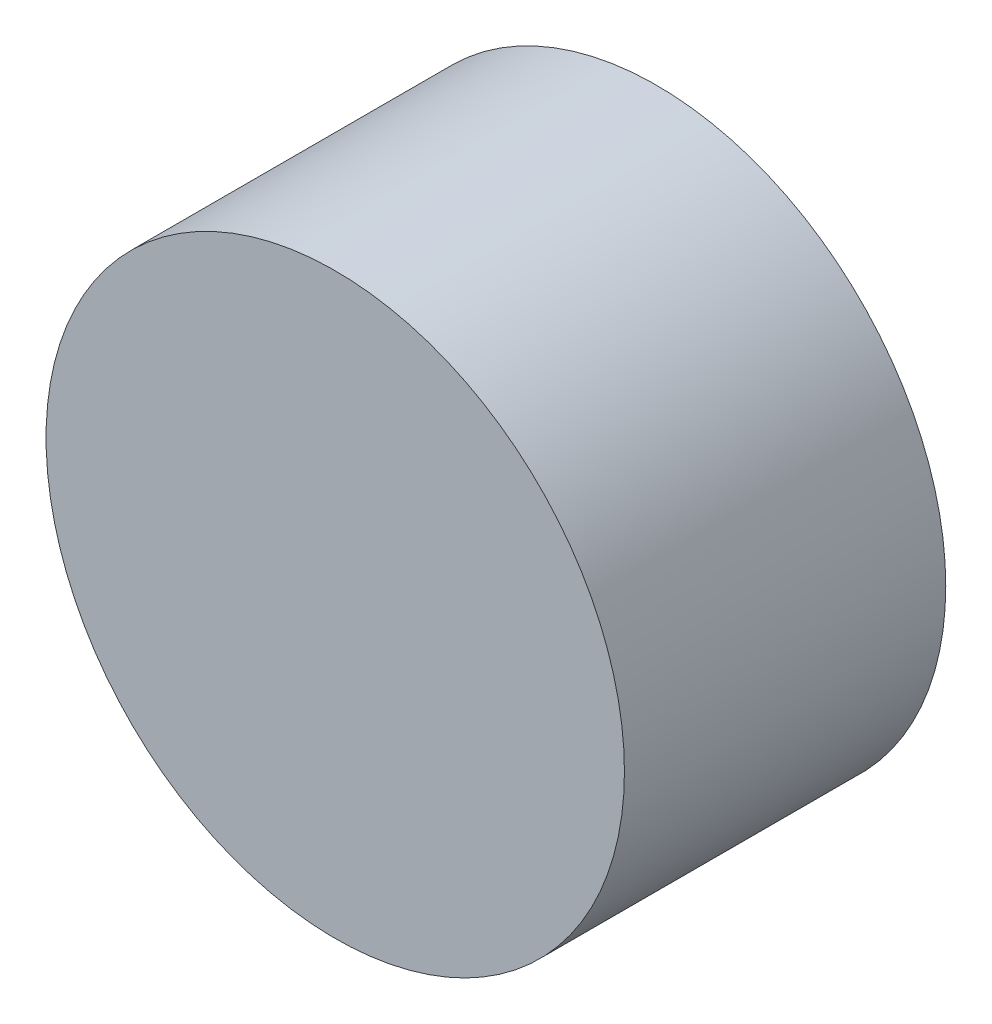
SolidWorks part; units mm, degrees
ref_plane "Front Plane" through (0, 0, 0) normal (0, 0, 1) x (1, 0, 0)
ref_plane "Top Plane" through (0, 0, 0) normal (0, 1, 0) x (1, 0, 0)
ref_plane "Right Plane" through (0, 0, 0) normal (1, 0, 0) x (0, 0, -1)
sketch "Sketch1" plane through (0, 0, 0) normal (0, 0, 1) x (1, 0, 0)
  circle A0 centre (0, 0) radius 3.6
  dimension "D1" = 7.2
extrude "Boss-Extrude1" add sketch "Sketch1" along normal blind 4
ref_axis "Axis1" through (0, 0, -0.2) along (0, 0, 1)
